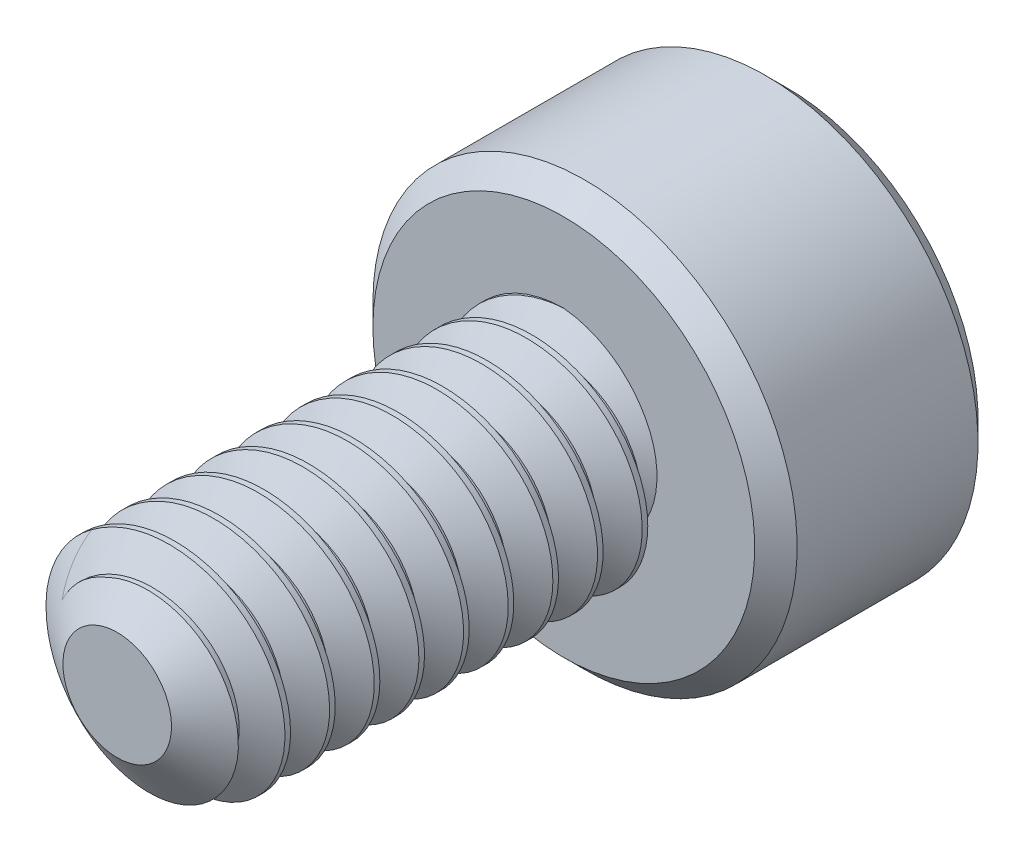
SolidWorks part; units mm, degrees
ref_plane "Front Plane" through (0, 0, 0) normal (0, 0, 1) x (1, 0, 0)
ref_plane "Top Plane" through (0, 0, 0) normal (0, 1, 0) x (1, 0, 0)
ref_plane "Right Plane" through (0, 0, 0) normal (1, 0, 0) x (0, 0, -1)
sketch "Sketch1" plane through (0, 0, 0) normal (0, 0, 1) x (1, 0, 0)
  circle A0 centre (0, 0) radius 1
  dimension "OD" = 2
extrude "Extrude1" add sketch "Sketch1" against normal blind 4
sketch "Sketch2" plane through (0, 0, 0) normal (0, 0, 1) x (1, 0, 0)
  circle A0 centre (0, 0) radius 1 construction
  circle A1 centre (0, 0) radius 1
curve "Helix/Spiral1" pitch 0.4 height 4.4 radius 1 centre (0, 0, 0) axis (0, 0, -1) start towards (0, 1, 0) parameters "pitch"=0.4
sketch "Sketch3" plane through (0, 0, 0) normal (1, 0, 0) x (0, 0, -1)
  line L0 (-0.35, 1) -> (-0.2, 0.7402)
  line L1 (-0.2, 0.7402) -> (-0.15, 0.7402)
  line L2 (-0.15, 0.7402) -> (0, 1)
  line L3 (-0.35, 1) -> (0, 1)
  line L4 (-0.175, 1) -> (-0.175, 0.7402) construction
  line L5 (-0.275, 0.8701) -> (-0.075, 0.8701) construction
  line L6 (0, 1) -> (0, -1) construction
  dimension "D1" = 0.05
  dimension "D2" = 0.2
  dimension "D3" = 60
sweep "Cut-Sweep1" cut profiles "Sketch3" path "Helix/Spiral1" align with end faces yes
sketch "Sketch4" plane through (0, 0, 0) normal (1, 0, 0) x (0, 0, -1)
  line L0 (0.3598, 1) -> (0, 0.4862)
  line L1 (0, 0.4862) -> (0, 1)
  line L2 (0.3598, 1) -> (0, 1)
  line L3 (-0.35, 1) -> (0, 1) construction
  line L4 (0, 0) -> (7.0209, 0) construction
  dimension "D1" = 55
  dimension "D2" = 0.254
revolve "Cut-Revolve1" cut sketch "Sketch4" angle 360 about L4
sketch "Sketch6" plane through (0, 0, -4) normal (0, 0, -1) x (-1, 0, 0)
  circle A0 centre (0, 0) radius 1.9
  dimension "head dia" = 3.8
extrude "Extrude2" add sketch "Sketch6" along normal blind 2
sketch "Sketch7" plane through (0, 0, -6) normal (0, 0, -1) x (-1, 0, 0)
  line L1 (0, 0.866) -> (-0.75, 0.433)
  line L2 (-0.75, 0.433) -> (-0.75, -0.433)
  line L3 (-0.75, -0.433) -> (0, -0.866)
  line L4 (0, -0.866) -> (0.75, -0.433)
  line L5 (0.75, -0.433) -> (0.75, 0.433)
  line L6 (0.75, 0.433) -> (0, 0.866)
  circle A0 centre (0, 0) radius 0.75 construction
  dimension "hex dia" = 1.5
extrude "Cut-Extrude1" cut sketch "Sketch7" against normal blind 1.125
sketch "Sketch8" plane through (0, 0, -6) normal (0, 0, -1) x (-1, 0, 0)
  circle A0 centre (0, 0) radius 0.866
extrude "Cut-Extrude2" cut sketch "Sketch8" against normal through all draft 45
chamfer "Chamfer1" distance 0.19 angle 45 2 edges at (-1.9, 0, -6) (-1.9, 0, -4)
sketch "Sketch10" plane through (0, 0, -4) normal (0, 0, 1) x (1, 0, 0)
  circle A1 centre (0, 0) radius 1
  circle A2 centre (0, 0) radius 1
  dimension "D1" = 0
ref_plane "Plane1" through (0, 0, 0) normal (0, 0, 1) x (1, 0, 0)
extrude "partial thread" [suppressed] add sketch "Sketch10" along normal up to surface (36 mm away) separate body up to plane "Plane1"
chamfer "Chamfer2" [suppressed] distance 0.04 angle 45
combine bodies "Combine1" [suppressed] operation type add bodies to combine 107 108
sketch "Sketch9" plane through (0, 0, 0) normal (1, 0, 0) x (0, 0, -1)
  line L0 (0, 1) -> (0, -1) construction
  line L1 (1, 1) -> (1, -1) construction
  dimension "D1" = 1
equation "\"D3@Helix/Spiral1\" = \"screw length@Extrude1\"+\"pitch@Helix/Spiral1\""
equation "\"D1@Sketch3\" = \"pitch@Helix/Spiral1\"*.125"
equation "\"D2@Sketch3\" = \"pitch@Helix/Spiral1\"*.5"
equation "\"D1@Cut-Extrude1\" = \"hex dia@Sketch7\"*.75"
equation "\"D1@Chamfer1\" = \"head dia@Sketch6\"*.05"
equation "\"D1@Sketch9\" = \"pitch@Helix/Spiral1\"*2.5"
equation "\"D1@Chamfer2\"=\"OD@Sketch1\"*.02"
